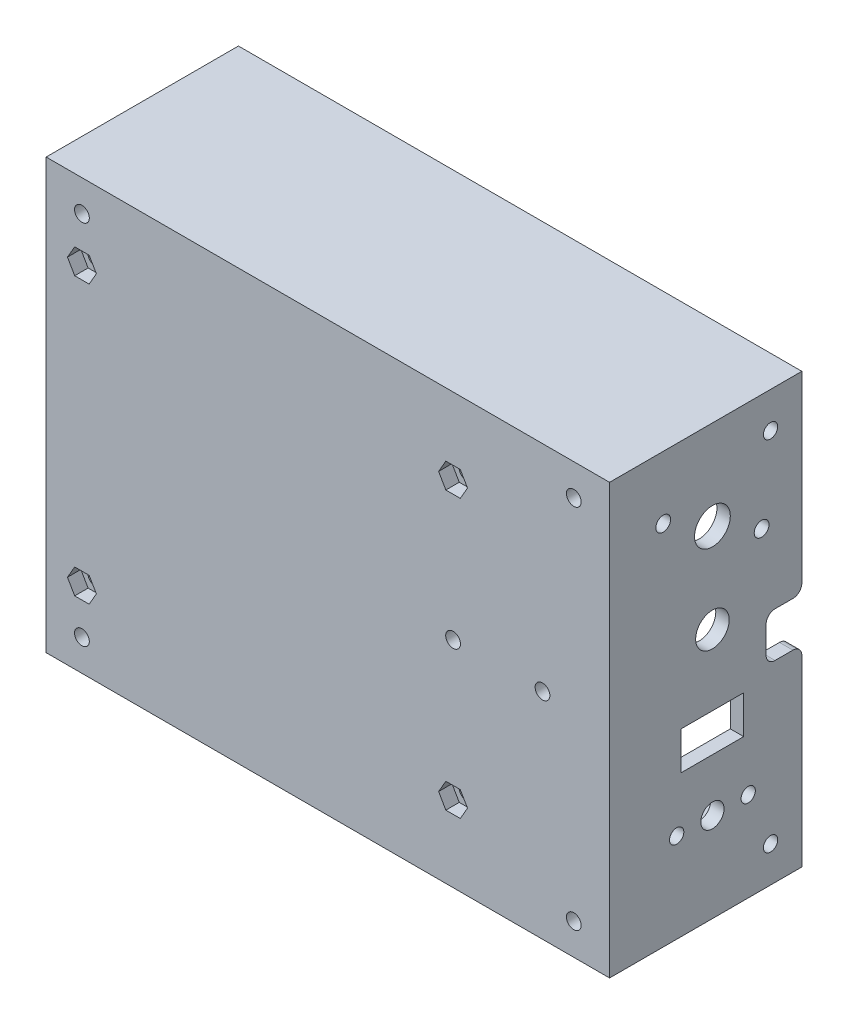
SolidWorks part; units mm, degrees
ref_plane "Front Plane" through (0, 0, 0) normal (0, 0, 1) x (1, 0, 0)
ref_plane "Top Plane" through (0, 0, 0) normal (0, 1, 0) x (1, 0, 0)
ref_plane "Right Plane" through (0, 0, 0) normal (1, 0, 0) x (0, 0, -1)
sketch "Sketch1" plane through (0, 0, 0) normal (0, 0, 1) x (1, 0, 0)
  line L1 (-60, -45) -> (60, -45)
  line L2 (-60, -45) -> (-60, 45)
  line L3 (-60, 45) -> (60, 45)
  line L4 (60, -45) -> (60, 45)
  line L5 (-60, -45) -> (60, 45) construction
  line L6 (-60, 45) -> (60, -45) construction
  line L7 (-55, -31) -> (28, -31)
  line L8 (-55, -31) -> (-55, 31)
  line L9 (-55, 31) -> (28, 31)
  line L10 (28, -31) -> (28, 31)
  line L11 (-55, -31) -> (28, 31) construction
  line L12 (-55, 31) -> (28, -31) construction
  circle A0 centre (-55, 31) radius 1.65
  circle A1 centre (28, 31) radius 1.65
  circle A2 centre (28, -31) radius 1.65
  circle A3 centre (-55, -31) radius 1.65
  circle A4 centre (-55, 41) radius 1.65
  circle A5 centre (55, 41) radius 1.65
  circle A6 centre (55, -41) radius 1.65
  circle A7 centre (-55, -41) radius 1.65
  point P0 (0, 0)
  point P6 (-13.5, 0)
  dimension "D7" = 3.3
  dimension "D8" = 4
  dimension "D9" = 5
  dimension "D10" = 5
  dimension "D11" = 4
  dimension "D12" = 3.3
  dimension "D13" = 5
  dimension "D14" = 4
  dimension "D15" = 4
  dimension "D16" = 5
  dimension "D1" = 90
  dimension "D2" = 120
  dimension "D3" = 62
  dimension "D4" = 83
  dimension "D5" = 14
  dimension "D6" = 5
extrude "Boss-Extrude2" add sketch "Sketch1" along normal blind 4 contours L1 L4 L3 L2 A3 L8 A0 L9 A1 L10 A2 L7 | A3 L7 A2 L10 A1 L9 A0 L8 region at (-58.5, 0, 0) region at (-13.5, 0, 0)
sketch "Sketch2" plane through (0, 0, 4) normal (0, 0, 1) x (1, 0, 0)
  line L1 (60, -45) -> (-60, -45)
  line L2 (60, -45) -> (60, 45)
  line L3 (60, 45) -> (-60, 45)
  line L4 (-60, -45) -> (-60, 45)
  line L5 (60, -45) -> (-60, 45) construction
  line L6 (60, 45) -> (-60, -45) construction
  line L7 (63, -48) -> (-63, -48)
  line L8 (63, -48) -> (63, 48)
  line L9 (63, 48) -> (-63, 48)
  line L10 (-63, -48) -> (-63, 48)
  line L11 (63, -48) -> (-63, 48) construction
  line L12 (63, 48) -> (-63, -48) construction
  point P0 (0, 0)
  point P7 (0, 0)
  dimension "D1" = 3
  dimension "D2" = 3
extrude "Boss-Extrude3" add sketch "Sketch2" against normal blind 43
sketch "Sketch3" plane through (-63, 0, 0) normal (-1, 0, 0) x (0, 0, 1)
  line L0 (-39, 48) -> (-39, -48) construction
  line L1 (-39, 48) -> (4, 48) construction
  line L2 (-39, -48) -> (4, -48) construction
  circle A0 centre (-32, -40) radius 1.6
  circle A1 centre (-32, 40) radius 1.6
  dimension "D1" = 3.2
  dimension "D2" = 7
  dimension "D3" = 8
  dimension "D4" = 8
  dimension "D5" = 7
  dimension "D6" = 3.2
extrude "Cut-Extrude1" cut sketch "Sketch3" against normal up to surface (126 mm away) up to face at (63, 0, -17.5)
sketch "Sketch4" plane through (63, 0, 0) normal (1, 0, 0) x (0, 0, -1)
  line L0 (39, -48) -> (39, 48) construction
  line L1 (39, 5) -> (31, 5)
  line L2 (39, 5) -> (39, -5)
  line L3 (39, -5) -> (31, -5)
  line L4 (31, 5) -> (31, -5)
  line L5 (39, -48) -> (-4, -48) construction
  line L6 (39, 48) -> (-4, 48) construction
  line L9 (12, -16.25) -> (26, -16.25)
  line L10 (12, -16.25) -> (12, -7.75)
  line L11 (12, -7.75) -> (26, -7.75)
  line L12 (26, -16.25) -> (26, -7.75)
  line L13 (12, -16.25) -> (26, -7.75) construction
  line L14 (12, -7.75) -> (26, -16.25) construction
  circle A1 centre (19, 8) radius 3.75
  point P8 (19, -12)
  dimension "D4" = 7.5
  dimension "D5" = 8.5
  dimension "D6" = 20
  dimension "D7" = 14
  dimension "D8" = 40
  dimension "D9" = 20
  dimension "D1" = 8
  dimension "D2" = 10
  dimension "D3" = 43
  dimension "D10" = 20
extrude "Cut-Extrude3" cut sketch "Sketch4" against normal blind 10
sketch "Sketch5" plane through (63, 0, 0) normal (1, 0, 0) x (0, 0, -1)
  line L0 (39, 5) -> (39, 48) construction
  line L1 (39, 48) -> (-4, 48) construction
  circle A0 centre (19, 28) radius 4
  dimension "D1" = 8
  dimension "D2" = 20
  dimension "D3" = 20
extrude "Cut-Extrude4" cut sketch "Sketch5" against normal blind 10
sketch "Sketch6" plane through (63, 0, 0) normal (1, 0, 0) x (0, 0, -1)
  line L0 (27, -28) -> (11, -28)
  line L1 (39, -48) -> (39, -5) construction
  line L3 (39, -48) -> (-4, -48) construction
  line L4 (-4, -48) -> (-4, 48) construction
  circle A0 centre (19, -28) radius 2.6
  circle A1 centre (11, -28) radius 1.6
  circle A2 centre (27, -28) radius 1.6
  point P3 (19, -28)
  dimension "D4" = 3.2
  dimension "D5" = 5.2
  dimension "D2" = 20
  dimension "D1" = 16
  dimension "D3" = 20
extrude "Cut-Extrude5" cut sketch "Sketch6" against normal blind 10 contours L0 A0 | A0 | A1 | A2 region at (63, -29.1035, -19)
sketch "Sketch8" plane through (0, 0, 0) normal (0, 0, -1) x (-1, 0, 0)
  line L0 (-60, 5) -> (-60, -5) construction
  circle A0 centre (-48, 0) radius 1.65
  circle A1 centre (-28, 0) radius 1.65
  circle A2 centre (-28, 31) radius 1.65 construction
  dimension "D1" = 3.3
  dimension "D2" = 3.3
  dimension "D3" = 20
  dimension "D4" = 31
  dimension "D5" = 31
  dimension "D6" = 12
extrude "Cut-Extrude6" cut sketch "Sketch8" against normal blind 10
sketch "Sketch9" plane through (0, 0, 0) normal (0, 0, -1) x (-1, 0, 0)
  line L0 (60, -45) -> (-60, -45) construction
  line L1 (-46.3834, 2.8) -> (-49.6166, 2.8)
  line L2 (-49.6166, 2.8) -> (-51.2332, 0)
  line L3 (-51.2332, 0) -> (-49.6166, -2.8)
  line L4 (-49.6166, -2.8) -> (-46.3834, -2.8)
  line L5 (-46.3834, -2.8) -> (-44.7668, 0)
  line L6 (-44.7668, 0) -> (-46.3834, 2.8)
  line L7 (-26.3834, 2.8) -> (-29.6166, 2.8)
  line L8 (-29.6166, 2.8) -> (-31.2332, 0)
  line L9 (-31.2332, 0) -> (-29.6166, -2.8)
  line L10 (-29.6166, -2.8) -> (-26.3834, -2.8)
  line L11 (-26.3834, -2.8) -> (-24.7668, 0)
  line L12 (-24.7668, 0) -> (-26.3834, 2.8)
  line L13 (-45.2287, 4.8) -> (-50.7713, 4.8)
  line L14 (-50.7713, 4.8) -> (-53.5426, 0)
  line L15 (-53.5426, 0) -> (-50.7713, -4.8)
  line L16 (-50.7713, -4.8) -> (-45.2287, -4.8)
  line L17 (-45.2287, -4.8) -> (-42.4574, 0)
  line L18 (-42.4574, 0) -> (-45.2287, 4.8)
  line L19 (-25.2287, 4.8) -> (-30.7713, 4.8)
  line L20 (-30.7713, 4.8) -> (-33.5426, 0)
  line L21 (-33.5426, 0) -> (-30.7713, -4.8)
  line L22 (-30.7713, -4.8) -> (-25.2287, -4.8)
  line L23 (-25.2287, -4.8) -> (-22.4574, 0)
  line L24 (-22.4574, 0) -> (-25.2287, 4.8)
  line L25 (60, -45) -> (-60, -45) construction
  line L26 (-51.7668, 41) -> (-53.3834, 43.8)
  line L27 (-53.3834, 43.8) -> (-56.6166, 43.8)
  line L28 (-56.6166, 43.8) -> (-58.2332, 41)
  line L29 (-58.2332, 41) -> (-56.6166, 38.2)
  line L30 (-56.6166, 38.2) -> (-53.3834, 38.2)
  line L31 (-53.3834, 38.2) -> (-51.7668, 41)
  line L32 (-50.6121, 41) -> (-52.8061, 44.8)
  line L33 (-52.8061, 44.8) -> (-57.1939, 44.8)
  line L34 (-57.1939, 44.8) -> (-59.3879, 41)
  line L35 (-59.3879, 41) -> (-57.1939, 37.2)
  line L36 (-57.1939, 37.2) -> (-52.8061, 37.2)
  line L37 (-52.8061, 37.2) -> (-50.6121, 41)
  line L38 (58.2332, 41) -> (56.6166, 43.8)
  line L39 (56.6166, 43.8) -> (53.3834, 43.8)
  line L40 (53.3834, 43.8) -> (51.7668, 41)
  line L41 (51.7668, 41) -> (53.3834, 38.2)
  line L42 (53.3834, 38.2) -> (56.6166, 38.2)
  line L43 (56.6166, 38.2) -> (58.2332, 41)
  line L44 (52.8061, 44.8) -> (50.6121, 41)
  line L45 (50.6121, 41) -> (52.8061, 37.2)
  line L46 (52.8061, 37.2) -> (57.1939, 37.2)
  line L47 (57.1939, 37.2) -> (59.3879, 41)
  line L48 (59.3879, 41) -> (57.1939, 44.8)
  line L49 (57.1939, 44.8) -> (52.8061, 44.8)
  line L50 (53.3834, -38.2) -> (51.7668, -41)
  line L51 (51.7668, -41) -> (53.3834, -43.8)
  line L52 (53.3834, -43.8) -> (56.6166, -43.8)
  line L53 (56.6166, -43.8) -> (58.2332, -41)
  line L54 (58.2332, -41) -> (56.6166, -38.2)
  line L55 (56.6166, -38.2) -> (53.3834, -38.2)
  line L56 (50.6121, -41) -> (52.8061, -44.8)
  line L57 (52.8061, -44.8) -> (57.1939, -44.8)
  line L58 (57.1939, -44.8) -> (59.3879, -41)
  line L59 (59.3879, -41) -> (57.1939, -37.2)
  line L60 (57.1939, -37.2) -> (52.8061, -37.2)
  line L61 (52.8061, -37.2) -> (50.6121, -41)
  line L62 (-53.3834, -38.2) -> (-56.6166, -38.2)
  line L63 (-56.6166, -38.2) -> (-58.2332, -41)
  line L64 (-58.2332, -41) -> (-56.6166, -43.8)
  line L65 (-56.6166, -43.8) -> (-53.3834, -43.8)
  line L66 (-53.3834, -43.8) -> (-51.7668, -41)
  line L67 (-51.7668, -41) -> (-53.3834, -38.2)
  line L68 (-52.8061, -37.2) -> (-57.1939, -37.2)
  line L69 (-57.1939, -37.2) -> (-59.3879, -41)
  line L70 (-59.3879, -41) -> (-57.1939, -44.8)
  line L71 (-57.1939, -44.8) -> (-52.8061, -44.8)
  line L72 (-52.8061, -44.8) -> (-50.6121, -41)
  line L73 (-50.6121, -41) -> (-52.8061, -37.2)
  circle A0 centre (-48, 0) radius 2.8 construction
  circle A1 centre (-28, 0) radius 2.8 construction
  circle A2 centre (-48, 0) radius 4.8 construction
  circle A3 centre (-28, 0) radius 4.8 construction
  circle A4 centre (-55, 41) radius 2.8 construction
  circle A5 centre (-55, 41) radius 3.8 construction
  circle A6 centre (55, 41) radius 2.8 construction
  circle A7 centre (55, 41) radius 3.8 construction
  circle A8 centre (55, -41) radius 2.8 construction
  circle A9 centre (55, -41) radius 3.8 construction
  circle A10 centre (-55, -41) radius 2.8 construction
  circle A11 centre (-55, -41) radius 3.8 construction
  dimension "D1" = 5.6
  dimension "D2" = 2
  dimension "D3" = 5.6
  dimension "D4" = 1
extrude "Boss-Extrude4" add sketch "Sketch9" along normal blind 3
sketch "Sketch10" plane through (0, 0, 4) normal (0, 0, 1) x (1, 0, 0)
  line L0 (63, 48) -> (-63, 48) construction
  line L1 (-51.7668, 31) -> (-53.3834, 33.8)
  line L2 (-53.3834, 33.8) -> (-56.6166, 33.8)
  line L3 (-56.6166, 33.8) -> (-58.2332, 31)
  line L4 (-58.2332, 31) -> (-56.6166, 28.2)
  line L5 (-56.6166, 28.2) -> (-53.3834, 28.2)
  line L6 (-53.3834, 28.2) -> (-51.7668, 31)
  line L7 (31.2332, 31) -> (29.6166, 33.8)
  line L8 (29.6166, 33.8) -> (26.3834, 33.8)
  line L9 (26.3834, 33.8) -> (24.7668, 31)
  line L10 (24.7668, 31) -> (26.3834, 28.2)
  line L11 (26.3834, 28.2) -> (29.6166, 28.2)
  line L12 (29.6166, 28.2) -> (31.2332, 31)
  line L25 (-51.7668, -31) -> (-53.3834, -28.2)
  line L26 (-53.3834, -28.2) -> (-56.6166, -28.2)
  line L27 (-56.6166, -28.2) -> (-58.2332, -31)
  line L28 (-58.2332, -31) -> (-56.6166, -33.8)
  line L29 (-56.6166, -33.8) -> (-53.3834, -33.8)
  line L30 (-53.3834, -33.8) -> (-51.7668, -31)
  line L31 (31.2332, -31) -> (29.6166, -28.2)
  line L32 (29.6166, -28.2) -> (26.3834, -28.2)
  line L33 (26.3834, -28.2) -> (24.7668, -31)
  line L34 (24.7668, -31) -> (26.3834, -33.8)
  line L35 (26.3834, -33.8) -> (29.6166, -33.8)
  line L36 (29.6166, -33.8) -> (31.2332, -31)
  circle A0 centre (-55, 31) radius 2.8 construction
  circle A1 centre (28, 31) radius 2.8 construction
  circle A4 centre (-55, -31) radius 2.8 construction
  circle A5 centre (28, -31) radius 2.8 construction
  dimension "D2" = 5.6
fillet "Fillet1" radius 2 4 edges at (61.5, 5, -31) (61.5, -5, -31) (61.5, -5, -39) (61.5, 5, -39)
extrude "Cut-Extrude8" cut sketch "Sketch10" against normal blind 3
sketch "Sketch12" plane through (0, 0, 0) normal (0, 0, -1) x (-1, 0, 0)
  circle A0 centre (-28, 31) radius 1.65
  circle A1 centre (55, 31) radius 1.65
  circle A2 centre (55, -31) radius 1.65
  circle A3 centre (-28, -31) radius 1.65
  circle A4 centre (-28, -31) radius 4
  circle A5 centre (55, -31) radius 4
  circle A6 centre (55, 31) radius 4
  circle A7 centre (-28, 31) radius 4
  dimension "D1" = 8
extrude "Boss-Extrude11" add sketch "Sketch12" along normal blind 5
sketch "Sketch13" plane through (60, 0, 0) normal (-1, 0, 0) x (0, 0, 1)
  line L1 (-25, 22) -> (-13, 22)
  line L2 (-25, 22) -> (-25, 34)
  line L3 (-25, 34) -> (-13, 34)
  line L4 (-13, 22) -> (-13, 34)
  line L5 (-25, 22) -> (-13, 34) construction
  line L6 (-25, 34) -> (-13, 22) construction
  line L7 (-35, 18) -> (-3, 18)
  line L8 (-35, 18) -> (-35, 38)
  line L9 (-35, 38) -> (-3, 38)
  line L10 (-3, 18) -> (-3, 38)
  line L11 (-35, 18) -> (-3, 38) construction
  line L12 (-35, 38) -> (-3, 18) construction
  point P0 (-19, 28)
  point P6 (-19, 28)
  dimension "D1" = 12
  dimension "D2" = 12
  dimension "D3" = 20
  dimension "D4" = 10
extrude "Boss-Extrude12" add sketch "Sketch13" along normal blind 2
chamfer "Chamfer1" distance 2 angle 45 2 edges at (58, 28, -3) (58, 28, -35)
sketch "Sketch14" plane through (58, 0, 0) normal (-1, 0, 0) x (0, 0, 1)
  line L2 (-33, 18) -> (-5, 18) construction
  line L3 (-35, 38) -> (-35, 18) construction
  line L4 (-3, 18) -> (-3, 38) construction
  line L5 (-5, 38) -> (-33, 38) construction
  circle A0 centre (-30, 22) radius 1.65
  circle A1 centre (-8, 34) radius 1.65
  dimension "D1" = 3.3
  dimension "D2" = 3.3
  dimension "D3" = 5
  dimension "D4" = 5
  dimension "D5" = 4
  dimension "D6" = 4
extrude "Cut-Extrude9" cut sketch "Sketch14" against normal blind 12
sketch "Sketch15" plane through (58, 0, 0) normal (-1, 0, 0) x (0, 0, 1)
  line L0 (-25, 34) -> (-25, 22) construction
  line L1 (-35, 38) -> (-28, 38)
  line L2 (-35, 38) -> (-35, 26)
  line L3 (-35, 26) -> (-28, 26)
  line L4 (-28, 38) -> (-28, 26)
  line L5 (-3, 18) -> (-10, 18)
  line L6 (-3, 18) -> (-3, 30)
  line L7 (-3, 30) -> (-10, 30)
  line L8 (-10, 18) -> (-10, 30)
  line L9 (-13, 22) -> (-13, 34) construction
  line L12 (-35, 38) -> (-35, 18) construction
  line L13 (-3, 18) -> (-3, 38) construction
  line L14 (-25, 22) -> (-13, 22) construction
  line L15 (-13, 34) -> (-25, 34) construction
  dimension "D1" = 4
  dimension "D2" = 3
  dimension "D3" = 3
  dimension "D4" = 4
extrude "Cut-Extrude10" cut sketch "Sketch15" against normal up to surface (2 mm away) up to face at (60, 22, -31.65)
chamfer "Chamfer3" distance 5 angle 45 1 edges at (59, 38, -28)
chamfer "Chamfer4" distance 5 angle 45 1 edges at (59, 18, -10)
chamfer "Chamfer5" distance 2 angle 45 1 edges at (58, 26.5, -10)
